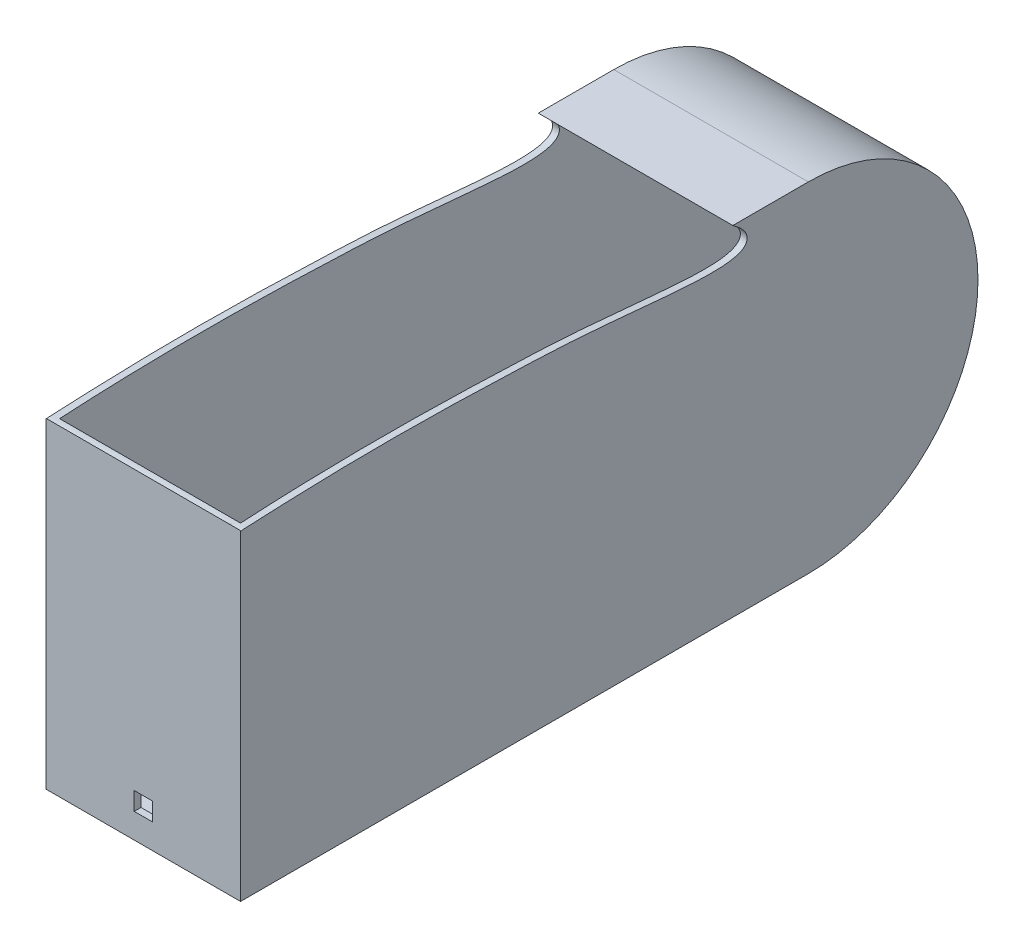
SolidWorks part; units mm, degrees
other "Markup1"
sketch "Sketch10" plane through (68.2625, 233.3625, 398.4625) normal (0.4688, 0.3088, 0.8276) x (0.8055, 0.235, -0.5439)
ref_plane "Front Plane" through (0, 0, 0) normal (0, 0, 1) x (1, 0, 0)
ref_plane "Top Plane" through (0, 0, 0) normal (0, 1, 0) x (1, 0, 0)
ref_plane "Right Plane" through (0, 0, 0) normal (1, 0, 0) x (0, 0, -1)
sketch "Sketch2" plane through (0, 0, 0) normal (1, 0, 0) x (0, 0, -1)
  line L0 (0, 0) -> (-393.7, 0)
  line L1 (-393.7, 0) -> (-393.7, 228.6)
  line L2 (-393.7, 228.6) -> (0, 228.6)
  line L4 (0, -4.7625) -> (-398.4625, -4.7625)
  line L5 (-398.4625, -4.7625) -> (-398.4625, 233.3625)
  line L6 (-398.4625, 233.3625) -> (0, 233.3625)
  arc A0 (0, 0) -> (0, 228.6) centre (0, 114.3) ccw
  arc A1 (0, -4.7625) -> (0, 233.3625) centre (0, 114.3) ccw
  dimension "D1" = 228.6
  dimension "D3" = 393.7
  dimension "D2" = 4.7625
extrude "Boss-Extrude1" add sketch "Sketch2" along normal blind 63.5 and the other way blind 63.5
sketch "Sketch4" plane through (0, 0, 398.4625) normal (0, 0, 1) x (1, 0, 0)
  line L0 (0, -130.9688) -> (0, 130.9688) construction
  line L2 (-6.35, 25.4) -> (6.35, 25.4)
  line L3 (69.85, 0) -> (-69.85, 0) construction
  line L4 (-6.35, 25.4) -> (-6.35, 12.7)
  line L5 (-6.35, 12.7) -> (6.35, 12.7)
  line L6 (6.35, 25.4) -> (6.35, 12.7)
  dimension "D3" = 12.7
  dimension "D4" = 12.7
  dimension "D5" = 12.7
  dimension "D6" = 6.35
extrude "Cut-Extrude1" cut sketch "Sketch4" against normal up to next
sketch "Sketch9" plane through (63.5, 0, 0) normal (1, 0, 0) x (0, 0, -1)
  line L0 (0, 69.85) -> (0, -69.85) construction
  line L1 (-398.4625, 233.3625) -> (0, 233.3625)
  line L2 (-398.4625, 233.3625) -> (-398.4625, -4.7625)
  line L3 (-398.4625, -4.7625) -> (0, -4.7625)
  arc A0 (0, -4.7625) -> (0, 233.3625) centre (0, 114.3) ccw
  arc A1 (0, -4.7625) -> (0, 233.3625) centre (0, 114.3) ccw construction
extrude "Boss-Extrude3" add sketch "Sketch9" along normal blind 4.7625
mirror "Mirror1" about plane through (0, 0, 0) normal (1, 0, 0) of "Boss-Extrude3"
curve "Curve4"
  spline degree 3 poles (0, 0.0315, 25.4063) (0, 0.0393, 25.3837) (0, 0.0703, 25.2937) (0, 0.1399, 25.0921) (0, 0.2522, 24.7577) (0, 0.405, 24.2942) (0, 0.5921, 23.7055) (0, 0.8077, 22.997) (0, 1.0451, 22.1758) (0, 1.2966, 21.2496) (0, 1.5548, 20.228) (0, 1.8116, 19.121) (0, 2.0603, 17.9406) (0, 2.2931, 16.6991) (0, 2.5029, 15.4099) (0, 2.6845, 14.087) (0, 2.832, 12.7455) (0, 2.9406, 11.3997) (0, 3.012, 10.0556) (0, 3.0204, 8.7276) (0, 2.9555, 7.4344) (0, 2.8238, 6.2027) (0, 2.6331, 5.0487) (0, 2.3917, 3.9878) (0, 2.1114, 3.0332) (0, 1.8047, 2.1961) (0, 1.4841, 1.4854) (0, 1.1619, 0.9079) (0, 0.8495, 0.4662) (0, 0.5537, 0.1626) (0, 0.2735, -0.0122) (0, -0.0084, -0.028) (0, -0.2343, 0.1391) (0, -0.3758, 0.4322) (0, -0.4687, 0.835) (0, -0.5173, 1.354) (0, -0.5271, 1.984) (0, -0.502, 2.719) (0, -0.4482, 3.5507) (0, -0.3722, 4.4705) (0, -0.2826, 5.4695) (0, -0.187, 6.5387) (0, -0.0938, 7.6688) (0, -0.0116, 8.8505) (0, 0.0504, 10.0833) (0, 0.0941, 11.3564) (0, 0.1392, 12.6563) (0, 0.1753, 13.9604) (0, 0.2014, 15.2542) (0, 0.216, 16.5239) (0, 0.2186, 17.7555) (0, 0.21, 18.9353) (0, 0.192, 20.05) (0, 0.1653, 21.0867) (0, 0.1345, 22.0333) (0, 0.1002, 22.8789) (0, 0.0674, 23.6118) (0, 0.0327, 24.228) (0, 0.0159, 24.706) (0, -0.0269, 25.0741) (0, -0.0004, 25.2565) (0, -0.052, 25.3969) (0, -0.0123, 25.3993) (0, 0, 25.4) knots 0 0 0 0 0.001372 0.005465 0.012235 0.021602 0.033461 0.047671 0.064081 0.082496 0.102719 0.124527 0.147676 0.171913 0.196978 0.222597 0.248497 0.274385 0.300041 0.32569 0.350525 0.37428 0.396711 0.417577 0.436654 0.453744 0.46868 0.481329 0.491631 0.499616 0.505546 0.510185 0.514824 0.520702 0.528516 0.538466 0.550543 0.564643 0.580638 0.598345 0.617584 0.638174 0.659922 0.682632 0.706121 0.730727 0.7557 0.780732 0.805564 0.829932 0.85357 0.876213 0.89761 0.917519 0.935698 0.951943 0.966047 0.97784 0.987174 0.993932 0.998018 0.999386 1 1 1 1
sketch "Sketch11" plane through (0, 0, 0) normal (1, 0, 0) x (0, 0, -1)
  line L0 (-398.4625, 220.6625) -> (-398.5494, 221.1035)
  line L1 (-398.4625, 220.6625) -> (-42.9494, 220.6625) construction
  line L2 (-42.9494, 220.6625) -> (-42.9494, -4.859) construction
  line L5 (0, 233.3625) -> (-398.4625, 233.3625) construction
  spline S1 degree 3 poles (-398.5494, 221.1035) (-398.2327, 221.211) (-396.9709, 221.6395) (-394.1464, 222.6005) (-389.463, 224.1503) (-382.97, 226.2597) (-374.7232, 228.8414) (-364.8, 231.8139) (-353.298, 235.0832) (-340.328, 238.5453) (-326.0211, 242.0946) (-310.5214, 245.6175) (-293.9949, 249.0248) (-276.6145, 252.2043) (-258.5679, 255.0613) (-240.0533, 257.5202) (-221.2792, 259.5005) (-202.4471, 260.9376) (-183.6418, 261.8532) (-165.0661, 261.8892) (-146.9801, 260.9024) (-129.7588, 258.985) (-113.6296, 256.2468) (-98.8045, 252.8051) (-85.4687, 248.8255) (-73.7775, 244.4846) (-63.8562, 239.9564) (-55.7982, 235.4141) (-49.6386, 231.0172) (-45.4101, 226.8608) (-42.9829, 222.9313) (-42.7786, 218.9863) (-45.1304, 215.8367) (-49.2377, 213.876) (-54.8785, 212.6017) (-62.1414, 211.9526) (-70.9545, 211.8549) (-81.2336, 212.2509) (-92.8634, 213.0536) (-105.7247, 214.1735) (-119.6932, 215.4886) (-134.6432, 216.8909) (-150.4457, 218.2642) (-166.97, 219.4865) (-184.2113, 220.4285) (-202.0158, 221.1186) (-220.1958, 221.8293) (-238.4357, 222.4132) (-256.5319, 222.8575) (-274.2916, 223.14) (-291.5192, 223.252) (-308.0225, 223.2033) (-323.6156, 223.0206) (-338.1184, 222.7108) (-351.3607, 222.3381) (-363.1914, 221.909) (-373.4448, 221.4958) (-382.0662, 221.0477) (-388.7536, 220.8417) (-393.9056, 220.2665) (-396.4559, 220.6486) (-398.423, 219.9346) (-398.4531, 220.4902) (-398.4625, 220.6625) knots 0 0 0 0 0.001372 0.005465 0.012235 0.021602 0.033461 0.047671 0.064081 0.082496 0.102719 0.124527 0.147676 0.171913 0.196978 0.222597 0.248497 0.274385 0.300041 0.32569 0.350525 0.37428 0.396711 0.417577 0.436654 0.453744 0.46868 0.481329 0.491631 0.499616 0.505546 0.510185 0.514824 0.520702 0.528516 0.538466 0.550543 0.564643 0.580638 0.598345 0.617584 0.638174 0.659922 0.682632 0.706121 0.730727 0.7557 0.780732 0.805564 0.829932 0.85357 0.876213 0.89761 0.917519 0.935698 0.951943 0.966047 0.97784 0.987174 0.993932 0.998018 0.999386 1 1 1 1
  dimension "D1" = 355.6
  dimension "D2" = 12.7
extrude "Cut-Extrude2" cut sketch "Sketch11" against normal up to next and the other way up to next contours S1 L0
sketch "Sketch12" plane through (-68.2625, 0, 0) normal (-1, 0, 0) x (0, 0, 1)
  line L2 (398.4625, 221.133) -> (398.4625, 233.3625)
  line L3 (398.4625, 233.3625) -> (359.3238, 233.3625)
  line L4 (398.4625, 221.133) -> (398.4625, 233.3625)
  line L5 (398.4625, 233.3625) -> (359.3238, 233.3625)
  spline S1 degree 3 poles (-392.334, -2188.3915) (-1069.6751, -144.6055) (-240.4055, 413.103) (374.7232, 228.8414) (382.97, 226.2597) (389.463, 224.1503) (394.1464, 222.6005) (525.2102, 178.0104) (657.0456, 141.0094) (-143.8105, -2712.4498) knots -2.598532 -2.598532 -2.598532 -2.598532 0.008638 0.022848 0.034707 0.044074 0.050844 0.054938 0.611803 0.611803 0.611803 0.611803 only from (359.3238, 233.3625) to (398.4625, 221.133)
  spline S2 degree 3 poles (359.3238, 233.3625) (361.3206, 232.7955) (366.6449, 231.2612) (374.7232, 228.8414) (382.97, 226.2597) (389.463, 224.1503) (394.1464, 222.6005) (396.9419, 221.6494) (398.1748, 221.2307) (398.4625, 221.133) knots 0.000125 0.000125 0.000125 0.000125 0.008638 0.022848 0.034707 0.044074 0.050844 0.054938 0.056184 0.056184 0.056184 0.056184
  dimension "D1" = 0
extrude "Cut-Extrude3" cut sketch "Sketch12" against normal up to next (136.525 mm away)
ref_plane "Plane1" through (0, 220.6625, 0) normal (0, 1, 0) x (1, 0, 0)
equation "\"fuselage_height\"=9"
equation "\"D1@Sketch2\"=\"fuselage_height\""
equation "\"fuselage_length\"=15.5"
equation "\"D3@Sketch2\"= \"fuselage_length\""
